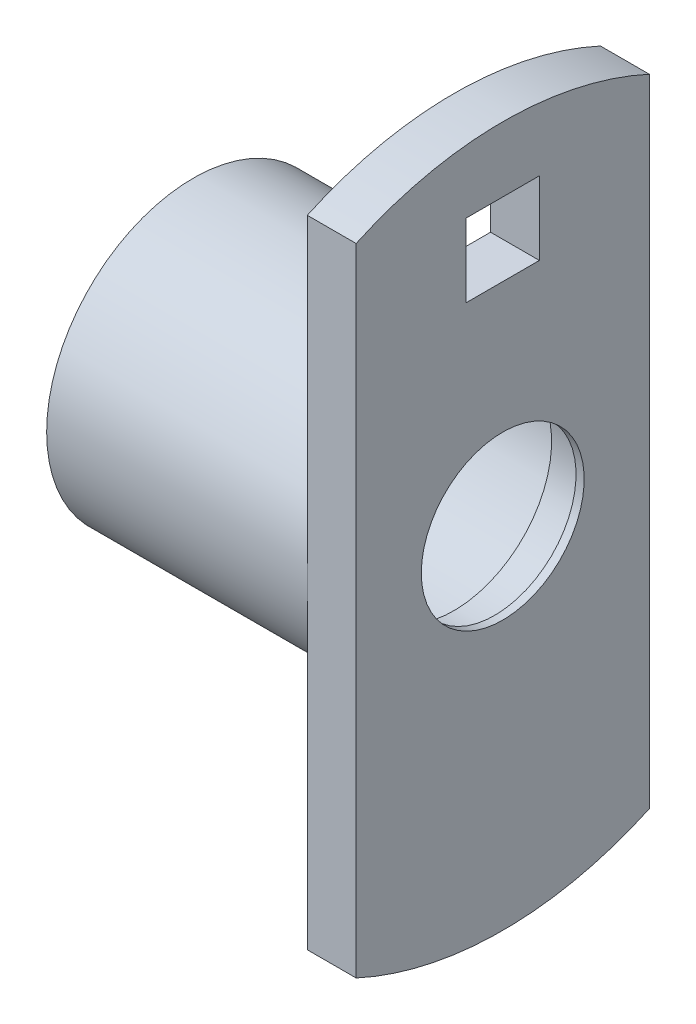
SolidWorks part; units mm, degrees
ref_plane "Front Plane" through (0, 0, 0) normal (0, 0, 1) x (1, 0, 0)
ref_plane "Top Plane" through (0, 0, 0) normal (0, 1, 0) x (1, 0, 0)
ref_plane "Right Plane" through (0, 0, 0) normal (1, 0, 0) x (0, 0, -1)
sketch "Sketch3" plane through (0, 0, 0) normal (0, 0, 1) x (1, 0, 0)
  line L0 (-15.4261, 0) -> (15.4261, 0) construction
  line L1 (0, -10.1639) -> (0, 10.1639) construction
sketch "Sketch1" plane through (0, 0, 0) normal (0, 0, 1) x (1, 0, 0)
  line L0 (-42.8096, 0) -> (42.8096, 0) construction
  line L1 (-1, 12) -> (-6, 12)
  line L2 (-6, 12) -> (-6, 16)
  line L3 (-6, 16) -> (-38, 16)
  line L4 (-38, 16) -> (-38, 18)
  line L6 (0, 43) -> (0, 10)
  line L9 (0, 10) -> (-1, 10)
  line L10 (-1, 10) -> (-1, 12)
  line L11 (-38, 18) -> (-6, 18)
  line L12 (-6, 18) -> (-6, 43)
  line L13 (-6, 43) -> (0, 43)
  point P3 (0, 0)
  dimension "D1" = 2
  dimension "D2" = 6
  dimension "D3" = 5
  dimension "D4" = 24
  dimension "D5" = 32
  dimension "D6" = 2
  dimension "D7" = 86
  dimension "D8" = 6
  dimension "D9" = 32
revolve "Revolve1" add sketch "Sketch1" angle 360 about L0
sketch "Sketch2" plane through (0, 0, 0) normal (1, 0, 0) x (0, 0, -1)
  line L0 (0, 43) -> (0, 18) construction
  line L3 (0, 43) -> (0, 10) construction
  line L4 (-18, 39.0512) -> (-18, -39.0512)
  line L5 (-4.5, 26) -> (4.5, 26)
  line L6 (-4.5, 26) -> (-4.5, 35)
  line L7 (-4.5, 35) -> (4.5, 35)
  line L8 (4.5, 26) -> (4.5, 35)
  line L9 (-4.5, 26) -> (4.5, 35) construction
  line L10 (-4.5, 35) -> (4.5, 26) construction
  line L11 (18, -39.0512) -> (18, 39.0512)
  circle A0 centre (0, 0) radius 43 construction
  circle A1 centre (0, 0) radius 18 construction
  circle A3 centre (0, 0) radius 43
  point P2 (0, 0)
  point P3 (0, 30.5)
  point P5 (0, 30.5)
  dimension "D1" = 9
extrude "Cut-Extrude1" cut sketch "Sketch2" against normal up to surface (6 mm away) contours L4 A3 | L5 L8 L7 L6 | L11 A3 region at (0, 0, 28.3004) region at (0, 0, -28.3004) region at (0, 30.5, 0) up to face at (-6, 0, 18)
